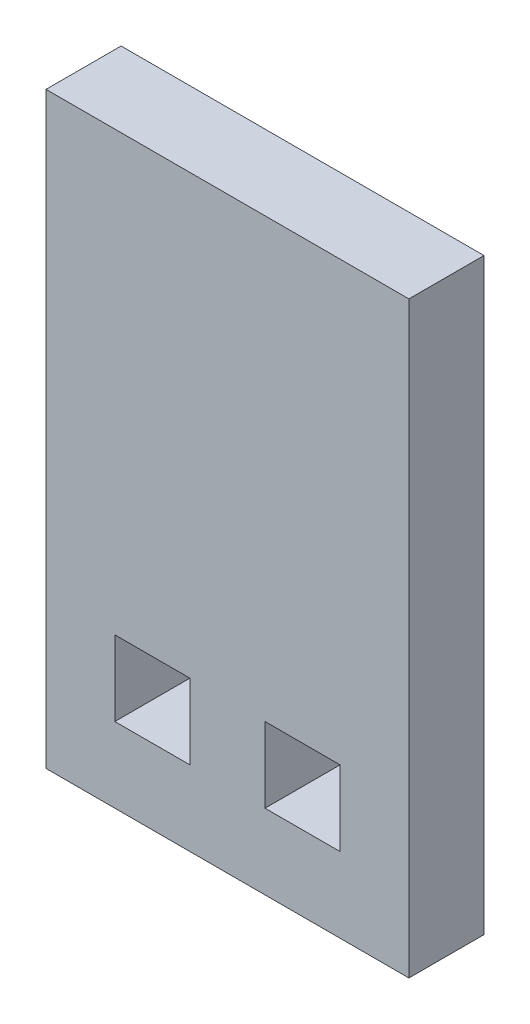
SolidWorks part; units mm, degrees
ref_plane "Front Plane" through (0, 0, 0) normal (0, 0, 1) x (1, 0, 0)
ref_plane "Top Plane" through (0, 0, 0) normal (0, 1, 0) x (1, 0, 0)
ref_plane "Right Plane" through (0, 0, 0) normal (1, 0, 0) x (0, 0, -1)
sketch "Sketch1" plane through (0, 0, 0) normal (0, 0, 1) x (1, 0, 0)
  line L0 (3.3883, -1.6786) -> (3.3883, -22.1739) construction
  line L6 (-3.8617, -22.1786) -> (-3.8617, -1.6786)
  line L7 (-3.8617, -1.6786) -> (10.6383, -1.6786)
  line L8 (10.6383, -22.1786) -> (10.6383, -1.6786)
  line L9 (-3.8617, -22.1786) -> (10.6383, -1.6786) construction
  line L10 (-3.8617, -1.6786) -> (10.6383, -22.1786) construction
  line L11 (-1.1117, -22.1786) -> (-1.1117, -19.1786)
  line L12 (-1.1117, -19.1786) -> (1.8883, -19.1786)
  line L13 (1.8883, -22.1786) -> (1.8883, -19.1786)
  line L14 (7.8883, -19.1786) -> (4.8883, -19.1786)
  line L15 (4.8883, -22.1786) -> (4.8883, -19.1786)
  line L16 (7.8883, -22.1786) -> (7.8883, -19.1786)
  line L19 (4.8883, -22.1786) -> (7.8883, -22.1786)
  line L32 (-1.1117, -22.1786) -> (1.8883, -22.1786)
  line L33 (-3.8617, -22.1786) -> (-3.8617, -25.1786)
  line L34 (-3.8617, -25.1786) -> (10.6383, -25.1786)
  line L35 (10.6383, -22.1786) -> (10.6383, -25.1786)
  point P0 (3.3883, -11.9286)
  dimension "D1" = 20.5
  dimension "D2" = 3
  dimension "D3" = 3
  dimension "D4" = 1.5
  dimension "D5" = 3
  dimension "D6" = 14.5
  dimension "D8" = 3
extrude "Boss-Extrude1" add sketch "Sketch1" along normal blind 3
